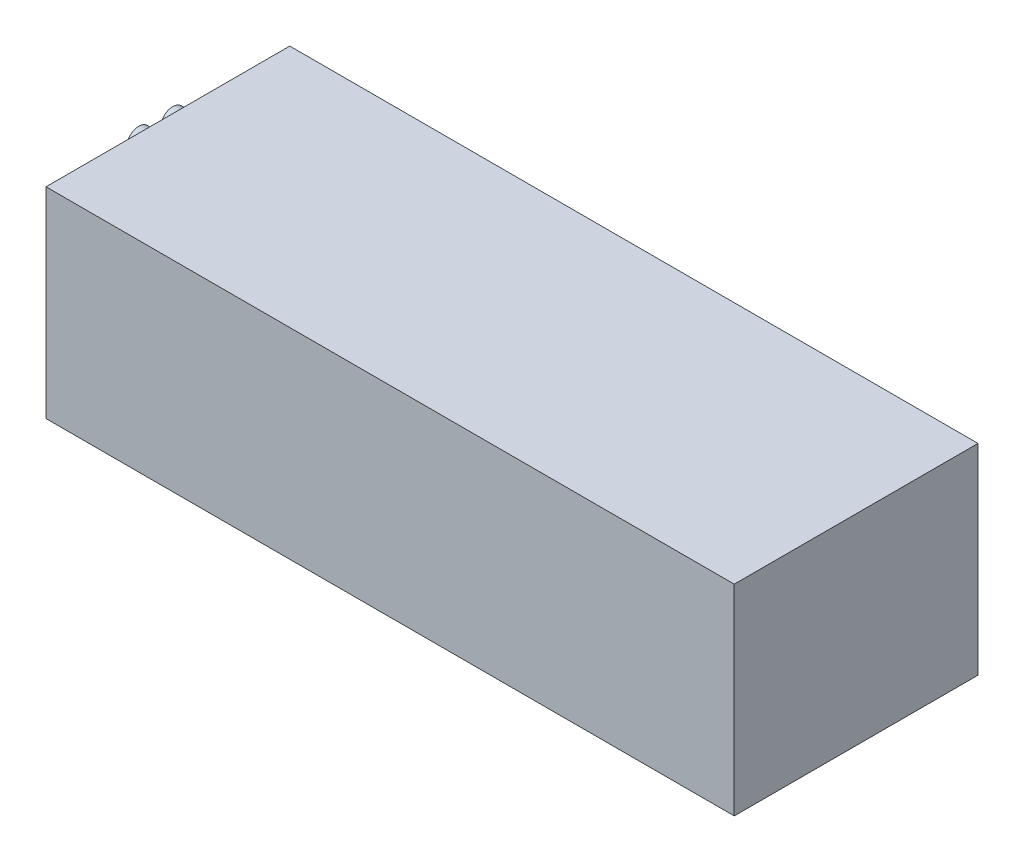
SolidWorks part; units mm, degrees
ref_plane "Front Plane" through (0, 0, 0) normal (0, 0, 1) x (1, 0, 0)
ref_plane "Top Plane" through (0, 0, 0) normal (0, 1, 0) x (1, 0, 0)
ref_plane "Right Plane" through (0, 0, 0) normal (1, 0, 0) x (0, 0, -1)
other "Center of Mass"
sketch "Sketch1" plane through (0, 0, 0) normal (0, 1, 0) x (1, 0, 0)
  line L5 (-72, -25.5) -> (72, -25.5)
  line L6 (-72, -25.5) -> (-72, 25.5)
  line L7 (-72, 25.5) -> (72, 25.5)
  line L8 (72, -25.5) -> (72, 25.5)
  line L9 (-72, -25.5) -> (72, 25.5) construction
  line L10 (-72, 25.5) -> (72, -25.5) construction
  point P0 (0, 0)
  dimension "D1" = 144
  dimension "D2" = 51
extrude "Boss-Extrude1" add sketch "Sketch1" along normal blind 41.9999 contours L7 L8 L5 L6
sketch "Sketch2" plane through (-72, 0, 0) normal (-1, 0, 0) x (0, 0, 1)
  line L0 (0, -23.1) -> (0, 23.1) construction
  line L1 (25.5, 41.9999) -> (-25.5, 41.9999) construction
  circle A0 centre (-3.556, 38.1899) radius 2.54
  circle A1 centre (3.556, 38.1899) radius 2.54
  dimension "D2" = 5.08
  dimension "D1" = 3.556
  dimension "D3" = 3.81
extrude "Boss-Extrude2" add sketch "Sketch2" along normal blind 2.54
sketch "Sketch3" plane through (-74.54, 0, 0) normal (-1, 0, 0) x (0, 0, 1)
  point P0 (3.556, 38.1899)
  point P1 (-3.556, 38.1899)
  point P3 (-3.556, 38.1899)
ref_plane "Plane1" through (-78.35, 0, 0) normal (-1, 0, 0) x (0, 0, 1)
sketch "Sketch4" plane through (-78.35, 0, 0) normal (-1, 0, 0) x (0, 0, 1)
  point P0 (-3.556, 38.1899)
  point P1 (3.556, 38.1899)
equation "\"Batt_Length\"=6"
equation "\"Batt_Height\"=2"
equation "\"Batt_Depth\"=1.65354"
equation "\"D1@Boss-Extrude1\"=\"Batt_Depth\""
